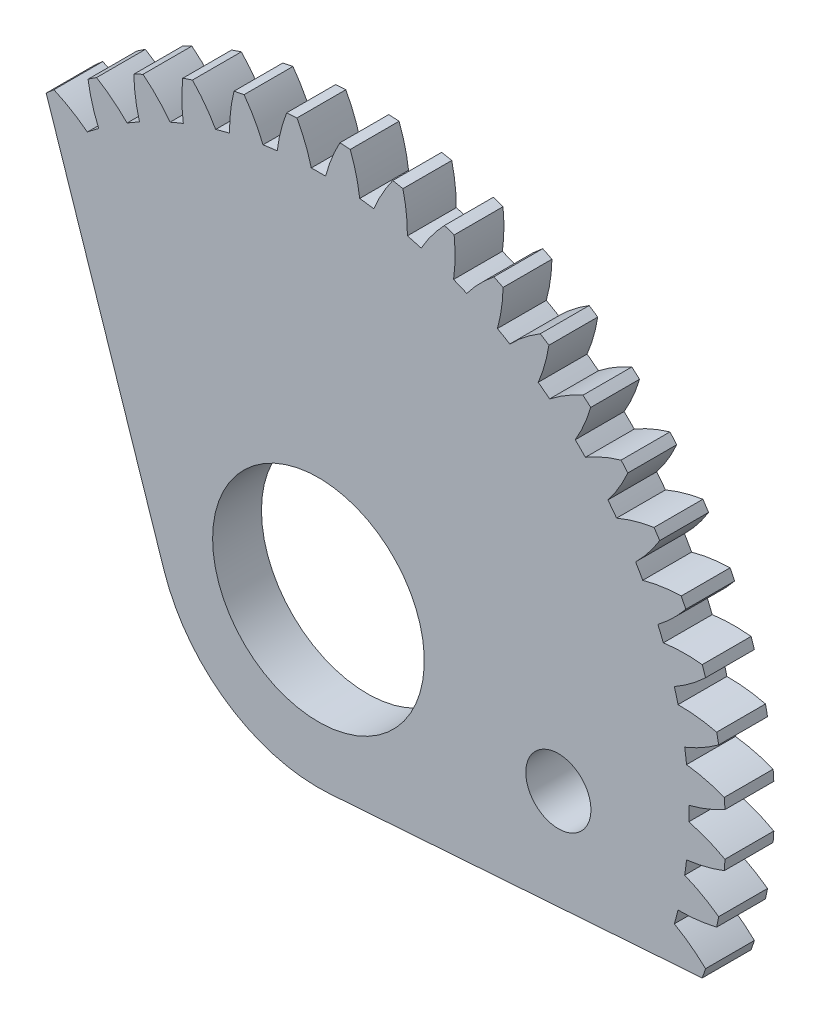
SolidWorks part; units mm, degrees
ref_plane "前视基准面" through (0, 0, 0) normal (0, 0, 1) x (1, 0, 0)
ref_plane "上视基准面" through (0, 0, 0) normal (0, 1, 0) x (1, 0, 0)
ref_plane "右视基准面" through (0, 0, 0) normal (1, 0, 0) x (0, 0, -1)
sketch "草图1" plane through (0, 0, 0) normal (0, 0, 1) x (1, 0, 0)
  arc A384 (-24.9651, 1.32) -> (-22.7448, 0.4395) centre (-20.3436, 9.7344) ccw
  arc A385 (-22.7448, 0.4395) -> (-22.7448, -0.4395) centre (0, 0) ccw
  arc A386 (-22.7448, -0.4395) -> (-24.9651, -1.32) centre (-20.3436, -9.7344) ccw
  arc A387 (-24.9651, -1.32) -> (-24.9238, -1.9499) centre (0, 0) ccw
  arc A388 (-24.9238, -1.9499) -> (-22.6075, -2.533) centre (-21.4402, 6.9957) ccw
  arc A389 (-22.6075, -2.533) -> (-22.4928, -3.4045) centre (0, 0) ccw
  arc A390 (-22.4928, -3.4045) -> (-24.5793, -4.5673) centre (-18.899, -12.3065) ccw
  arc A391 (-24.5793, -4.5673) -> (-24.4561, -5.1864) centre (0, 0) ccw
  arc A392 (-24.4561, -5.1864) -> (-22.0835, -5.4622) centre (-22.1699, 4.1374) ccw
  arc A393 (-22.0835, -5.4622) -> (-21.856, -6.3113) centre (0, 0) ccw
  arc A394 (-21.856, -6.3113) -> (-23.7728, -7.7365) centre (-17.131, -14.668) ccw
  arc A395 (-23.7728, -7.7365) -> (-23.5699, -8.3342) centre (0, 0) ccw
  arc A396 (-23.5699, -8.3342) -> (-21.1816, -8.298) centre (-22.5202, 1.2082) ccw
  arc A397 (-21.1816, -8.298) -> (-20.8452, -9.1101) centre (0, 0) ccw
  arc A398 (-20.8452, -9.1101) -> (-22.5596, -10.7733) centre (-15.0699, -16.7786) ccw
  arc A399 (-22.5596, -10.7733) -> (-22.2804, -11.3394) centre (0, 0) ccw
  arc A400 (-22.2804, -11.3394) -> (-19.9173, -10.9917) centre (-22.4853, -1.7416) ccw
  arc A401 (-19.9173, -10.9917) -> (-19.4778, -11.753) centre (0, 0) ccw
  arc A402 (-19.4778, -11.753) -> (-20.9604, -13.6257) centre (-12.7509, -18.602) ccw
  arc A403 (-20.9604, -13.6257) -> (-20.6097, -14.1506) centre (0, 0) ccw
  arc A404 (-20.6097, -14.1506) -> (-18.3122, -13.4974) centre (-22.0656, -4.6616) ccw
  arc A405 (-18.3122, -13.4974) -> (-17.7771, -14.1948) centre (0, 0) ccw
  arc A406 (-17.7771, -14.1948) -> (-19.0026, -16.245) centre (-10.2138, -20.1072) ccw
  arc A407 (-19.0026, -16.245) -> (-18.5864, -16.7196) centre (0, 0) ccw
  arc A408 (-18.5864, -16.7196) -> (-16.3938, -15.7722) centre (-21.2684, -7.5019) ccw
  arc A409 (-16.3938, -15.7722) -> (-15.7722, -16.3938) centre (0, 0) ccw
  arc A410 (-15.7722, -16.3938) -> (-16.7196, -18.5864) centre (-7.5019, -21.2684) ccw
  arc A411 (-16.7196, -18.5864) -> (-16.245, -19.0026) centre (0, 0) ccw
  arc A412 (-16.245, -19.0026) -> (-14.1948, -17.7771) centre (-20.1072, -10.2138) ccw
  arc A413 (-14.1948, -17.7771) -> (-13.4974, -18.3122) centre (0, 0) ccw
  arc A414 (-13.4974, -18.3122) -> (-14.1506, -20.6097) centre (-4.6616, -22.0656) ccw
  arc A415 (-14.1506, -20.6097) -> (-13.6257, -20.9604) centre (0, 0) ccw
  arc A416 (-13.6257, -20.9604) -> (-11.753, -19.4778) centre (-18.602, -12.7509) ccw
  arc A417 (-11.753, -19.4778) -> (-10.9917, -19.9173) centre (0, 0) ccw
  arc A418 (-10.9917, -19.9173) -> (-11.3394, -22.2804) centre (-1.7416, -22.4853) ccw
  arc A419 (-11.3394, -22.2804) -> (-10.7733, -22.5596) centre (0, 0) ccw
  arc A420 (-10.7733, -22.5596) -> (-9.1101, -20.8452) centre (-16.7786, -15.0699) ccw
  arc A421 (-9.1101, -20.8452) -> (-8.298, -21.1816) centre (0, 0) ccw
  arc A422 (-8.298, -21.1816) -> (-8.3342, -23.5699) centre (1.2082, -22.5202) ccw
  arc A423 (-8.3342, -23.5699) -> (-7.7365, -23.7728) centre (0, 0) ccw
  arc A424 (-7.7365, -23.7728) -> (-6.3113, -21.856) centre (-14.668, -17.131) ccw
  arc A425 (-6.3113, -21.856) -> (-5.4622, -22.0835) centre (0, 0) ccw
  arc A426 (-5.4622, -22.0835) -> (-5.1864, -24.4561) centre (4.1374, -22.1699) ccw
  arc A427 (-5.1864, -24.4561) -> (-4.5673, -24.5793) centre (0, 0) ccw
  arc A428 (-4.5673, -24.5793) -> (-3.4045, -22.4928) centre (-12.3065, -18.899) ccw
  arc A429 (-3.4045, -22.4928) -> (-2.533, -22.6075) centre (0, 0) ccw
  arc A430 (-2.533, -22.6075) -> (-1.9499, -24.9238) centre (6.9957, -21.4402) ccw
  arc A431 (-1.9499, -24.9238) -> (-1.32, -24.9651) centre (0, 0) ccw
  arc A432 (-1.32, -24.9651) -> (-0.4395, -22.7448) centre (-9.7344, -20.3436) ccw
  arc A433 (-0.4395, -22.7448) -> (0.4395, -22.7448) centre (0, 0) ccw
  arc A434 (0.4395, -22.7448) -> (1.32, -24.9651) centre (9.7344, -20.3436) ccw
  arc A435 (1.32, -24.9651) -> (1.9499, -24.9238) centre (0, 0) ccw
  arc A436 (1.9499, -24.9238) -> (2.533, -22.6075) centre (-6.9957, -21.4402) ccw
  arc A437 (2.533, -22.6075) -> (3.4045, -22.4928) centre (0, 0) ccw
  arc A438 (3.4045, -22.4928) -> (4.5673, -24.5793) centre (12.3065, -18.899) ccw
  arc A439 (4.5673, -24.5793) -> (5.1864, -24.4561) centre (0, 0) ccw
  arc A440 (5.1864, -24.4561) -> (5.4622, -22.0835) centre (-4.1374, -22.1699) ccw
  arc A441 (5.4622, -22.0835) -> (6.3113, -21.856) centre (0, 0) ccw
  arc A442 (6.3113, -21.856) -> (7.7365, -23.7728) centre (14.668, -17.131) ccw
  arc A443 (7.7365, -23.7728) -> (8.3342, -23.5699) centre (0, 0) ccw
  arc A444 (8.3342, -23.5699) -> (8.298, -21.1816) centre (-1.2082, -22.5202) ccw
  arc A445 (8.298, -21.1816) -> (9.1101, -20.8452) centre (0, 0) ccw
  arc A446 (9.1101, -20.8452) -> (10.7733, -22.5596) centre (16.7786, -15.0699) ccw
  arc A447 (10.7733, -22.5596) -> (11.3394, -22.2804) centre (0, 0) ccw
  arc A448 (11.3394, -22.2804) -> (10.9917, -19.9173) centre (1.7416, -22.4853) ccw
  arc A449 (10.9917, -19.9173) -> (11.753, -19.4778) centre (0, 0) ccw
  arc A450 (11.753, -19.4778) -> (13.6257, -20.9604) centre (18.602, -12.7509) ccw
  arc A451 (13.6257, -20.9604) -> (14.1506, -20.6097) centre (0, 0) ccw
  arc A452 (14.1506, -20.6097) -> (13.4974, -18.3122) centre (4.6616, -22.0656) ccw
  arc A453 (13.4974, -18.3122) -> (14.1948, -17.7771) centre (0, 0) ccw
  arc A454 (14.1948, -17.7771) -> (16.245, -19.0026) centre (20.1072, -10.2138) ccw
  arc A455 (16.245, -19.0026) -> (16.7196, -18.5864) centre (0, 0) ccw
  arc A456 (16.7196, -18.5864) -> (15.7722, -16.3938) centre (7.5019, -21.2684) ccw
  arc A457 (15.7722, -16.3938) -> (16.3938, -15.7722) centre (0, 0) ccw
  arc A458 (16.3938, -15.7722) -> (18.5864, -16.7196) centre (21.2684, -7.5019) ccw
  arc A459 (18.5864, -16.7196) -> (19.0026, -16.245) centre (0, 0) ccw
  arc A460 (19.0026, -16.245) -> (17.7771, -14.1948) centre (10.2138, -20.1072) ccw
  arc A461 (17.7771, -14.1948) -> (18.3122, -13.4974) centre (0, 0) ccw
  arc A462 (18.3122, -13.4974) -> (20.6097, -14.1506) centre (22.0656, -4.6616) ccw
  arc A463 (20.6097, -14.1506) -> (20.9604, -13.6257) centre (0, 0) ccw
  arc A464 (20.9604, -13.6257) -> (19.4778, -11.753) centre (12.7509, -18.602) ccw
  arc A465 (19.4778, -11.753) -> (19.9173, -10.9917) centre (0, 0) ccw
  arc A466 (19.9173, -10.9917) -> (22.2804, -11.3394) centre (22.4853, -1.7416) ccw
  arc A467 (22.2804, -11.3394) -> (22.5596, -10.7733) centre (0, 0) ccw
  arc A468 (22.5596, -10.7733) -> (20.8452, -9.1101) centre (15.0699, -16.7786) ccw
  arc A469 (20.8452, -9.1101) -> (21.1816, -8.298) centre (0, 0) ccw
  arc A470 (21.1816, -8.298) -> (23.5699, -8.3342) centre (22.5202, 1.2082) ccw
  arc A471 (23.5699, -8.3342) -> (23.7728, -7.7365) centre (0, 0) ccw
  arc A472 (23.7728, -7.7365) -> (21.856, -6.3113) centre (17.131, -14.668) ccw
  arc A473 (21.856, -6.3113) -> (22.0835, -5.4622) centre (0, 0) ccw
  arc A474 (22.0835, -5.4622) -> (24.4561, -5.1864) centre (22.1699, 4.1374) ccw
  arc A475 (24.4561, -5.1864) -> (24.5793, -4.5673) centre (0, 0) ccw
  arc A476 (24.5793, -4.5673) -> (22.4928, -3.4045) centre (18.899, -12.3065) ccw
  arc A477 (22.4928, -3.4045) -> (22.6075, -2.533) centre (0, 0) ccw
  arc A478 (22.6075, -2.533) -> (24.9238, -1.9499) centre (21.4402, 6.9957) ccw
  arc A479 (24.9238, -1.9499) -> (24.9651, -1.32) centre (0, 0) ccw
  arc A480 (24.9651, -1.32) -> (22.7448, -0.4395) centre (20.3436, -9.7344) ccw
  arc A481 (22.7448, -0.4395) -> (22.7448, 0.4395) centre (0, 0) ccw
  arc A482 (22.7448, 0.4395) -> (24.9651, 1.32) centre (20.3436, 9.7344) ccw
  arc A483 (24.9651, 1.32) -> (24.9238, 1.9499) centre (0, 0) ccw
  arc A484 (24.9238, 1.9499) -> (22.6075, 2.533) centre (21.4402, -6.9957) ccw
  arc A485 (22.6075, 2.533) -> (22.4928, 3.4045) centre (0, 0) ccw
  arc A486 (22.4928, 3.4045) -> (24.5793, 4.5673) centre (18.899, 12.3065) ccw
  arc A487 (24.5793, 4.5673) -> (24.4561, 5.1864) centre (0, 0) ccw
  arc A488 (24.4561, 5.1864) -> (22.0835, 5.4622) centre (22.1699, -4.1374) ccw
  arc A489 (22.0835, 5.4622) -> (21.856, 6.3113) centre (0, 0) ccw
  arc A490 (21.856, 6.3113) -> (23.7728, 7.7365) centre (17.131, 14.668) ccw
  arc A491 (23.7728, 7.7365) -> (23.5699, 8.3342) centre (0, 0) ccw
  arc A492 (23.5699, 8.3342) -> (21.1816, 8.298) centre (22.5202, -1.2082) ccw
  arc A493 (21.1816, 8.298) -> (20.8452, 9.1101) centre (0, 0) ccw
  arc A494 (20.8452, 9.1101) -> (22.5596, 10.7733) centre (15.0699, 16.7786) ccw
  arc A495 (22.5596, 10.7733) -> (22.2804, 11.3394) centre (0, 0) ccw
  arc A496 (22.2804, 11.3394) -> (19.9173, 10.9917) centre (22.4853, 1.7416) ccw
  arc A497 (19.9173, 10.9917) -> (19.4778, 11.753) centre (0, 0) ccw
  arc A498 (19.4778, 11.753) -> (20.9604, 13.6257) centre (12.7509, 18.602) ccw
  arc A499 (20.9604, 13.6257) -> (20.6097, 14.1506) centre (0, 0) ccw
  arc A500 (20.6097, 14.1506) -> (18.3122, 13.4974) centre (22.0656, 4.6616) ccw
  arc A501 (18.3122, 13.4974) -> (17.7771, 14.1948) centre (0, 0) ccw
  arc A502 (17.7771, 14.1948) -> (19.0026, 16.245) centre (10.2138, 20.1072) ccw
  arc A503 (19.0026, 16.245) -> (18.5864, 16.7196) centre (0, 0) ccw
  arc A504 (18.5864, 16.7196) -> (16.3938, 15.7722) centre (21.2684, 7.5019) ccw
  arc A505 (16.3938, 15.7722) -> (15.7722, 16.3938) centre (0, 0) ccw
  arc A506 (15.7722, 16.3938) -> (16.7196, 18.5864) centre (7.5019, 21.2684) ccw
  arc A507 (16.7196, 18.5864) -> (16.245, 19.0026) centre (0, 0) ccw
  arc A508 (16.245, 19.0026) -> (14.1948, 17.7771) centre (20.1072, 10.2138) ccw
  arc A509 (14.1948, 17.7771) -> (13.4974, 18.3122) centre (0, 0) ccw
  arc A510 (13.4974, 18.3122) -> (14.1506, 20.6097) centre (4.6616, 22.0656) ccw
  arc A511 (14.1506, 20.6097) -> (13.6257, 20.9604) centre (0, 0) ccw
  arc A512 (13.6257, 20.9604) -> (11.753, 19.4778) centre (18.602, 12.7509) ccw
  arc A513 (11.753, 19.4778) -> (10.9917, 19.9173) centre (0, 0) ccw
  arc A514 (10.9917, 19.9173) -> (11.3394, 22.2804) centre (1.7416, 22.4853) ccw
  arc A515 (11.3394, 22.2804) -> (10.7733, 22.5596) centre (0, 0) ccw
  arc A516 (10.7733, 22.5596) -> (9.1101, 20.8452) centre (16.7786, 15.0699) ccw
  arc A517 (9.1101, 20.8452) -> (8.298, 21.1816) centre (0, 0) ccw
  arc A518 (8.298, 21.1816) -> (8.3342, 23.5699) centre (-1.2082, 22.5202) ccw
  arc A519 (8.3342, 23.5699) -> (7.7365, 23.7728) centre (0, 0) ccw
  arc A520 (7.7365, 23.7728) -> (6.3113, 21.856) centre (14.668, 17.131) ccw
  arc A521 (6.3113, 21.856) -> (5.4622, 22.0835) centre (0, 0) ccw
  arc A522 (5.4622, 22.0835) -> (5.1864, 24.4561) centre (-4.1374, 22.1699) ccw
  arc A523 (5.1864, 24.4561) -> (4.5673, 24.5793) centre (0, 0) ccw
  arc A524 (4.5673, 24.5793) -> (3.4045, 22.4928) centre (12.3065, 18.899) ccw
  arc A525 (3.4045, 22.4928) -> (2.533, 22.6075) centre (0, 0) ccw
  arc A526 (2.533, 22.6075) -> (1.9499, 24.9238) centre (-6.9957, 21.4402) ccw
  arc A527 (1.9499, 24.9238) -> (1.32, 24.9651) centre (0, 0) ccw
  arc A528 (1.32, 24.9651) -> (0.4395, 22.7448) centre (9.7344, 20.3436) ccw
  arc A529 (0.4395, 22.7448) -> (-0.4395, 22.7448) centre (0, 0) ccw
  arc A530 (-0.4395, 22.7448) -> (-1.32, 24.9651) centre (-9.7344, 20.3436) ccw
  arc A531 (-1.32, 24.9651) -> (-1.9499, 24.9238) centre (0, 0) ccw
  arc A532 (-1.9499, 24.9238) -> (-2.533, 22.6075) centre (6.9957, 21.4402) ccw
  arc A533 (-2.533, 22.6075) -> (-3.4045, 22.4928) centre (0, 0) ccw
  arc A534 (-3.4045, 22.4928) -> (-4.5673, 24.5793) centre (-12.3065, 18.899) ccw
  arc A535 (-4.5673, 24.5793) -> (-5.1864, 24.4561) centre (0, 0) ccw
  arc A536 (-5.1864, 24.4561) -> (-5.4622, 22.0835) centre (4.1374, 22.1699) ccw
  arc A537 (-5.4622, 22.0835) -> (-6.3113, 21.856) centre (0, 0) ccw
  arc A538 (-6.3113, 21.856) -> (-7.7365, 23.7728) centre (-14.668, 17.131) ccw
  arc A539 (-7.7365, 23.7728) -> (-8.3342, 23.5699) centre (0, 0) ccw
  arc A540 (-8.3342, 23.5699) -> (-8.298, 21.1816) centre (1.2082, 22.5202) ccw
  arc A541 (-8.298, 21.1816) -> (-9.1101, 20.8452) centre (0, 0) ccw
  arc A542 (-9.1101, 20.8452) -> (-10.7733, 22.5596) centre (-16.7786, 15.0699) ccw
  arc A543 (-10.7733, 22.5596) -> (-11.3394, 22.2804) centre (0, 0) ccw
  arc A544 (-11.3394, 22.2804) -> (-10.9917, 19.9173) centre (-1.7416, 22.4853) ccw
  arc A545 (-10.9917, 19.9173) -> (-11.753, 19.4778) centre (0, 0) ccw
  arc A546 (-11.753, 19.4778) -> (-13.6257, 20.9604) centre (-18.602, 12.7509) ccw
  arc A547 (-13.6257, 20.9604) -> (-14.1506, 20.6097) centre (0, 0) ccw
  arc A548 (-14.1506, 20.6097) -> (-13.4974, 18.3122) centre (-4.6616, 22.0656) ccw
  arc A549 (-13.4974, 18.3122) -> (-14.1948, 17.7771) centre (0, 0) ccw
  arc A550 (-14.1948, 17.7771) -> (-16.245, 19.0026) centre (-20.1072, 10.2138) ccw
  arc A551 (-16.245, 19.0026) -> (-16.7196, 18.5864) centre (0, 0) ccw
  arc A552 (-16.7196, 18.5864) -> (-15.7722, 16.3938) centre (-7.5019, 21.2684) ccw
  arc A553 (-15.7722, 16.3938) -> (-16.3938, 15.7722) centre (0, 0) ccw
  arc A554 (-16.3938, 15.7722) -> (-18.5864, 16.7196) centre (-21.2684, 7.5019) ccw
  arc A555 (-18.5864, 16.7196) -> (-19.0026, 16.245) centre (0, 0) ccw
  arc A556 (-19.0026, 16.245) -> (-17.7771, 14.1948) centre (-10.2138, 20.1072) ccw
  arc A557 (-17.7771, 14.1948) -> (-18.3122, 13.4974) centre (0, 0) ccw
  arc A558 (-18.3122, 13.4974) -> (-20.6097, 14.1506) centre (-22.0656, 4.6616) ccw
  arc A559 (-20.6097, 14.1506) -> (-20.9604, 13.6257) centre (0, 0) ccw
  arc A560 (-20.9604, 13.6257) -> (-19.4778, 11.753) centre (-12.7509, 18.602) ccw
  arc A561 (-19.4778, 11.753) -> (-19.9173, 10.9917) centre (0, 0) ccw
  arc A562 (-19.9173, 10.9917) -> (-22.2804, 11.3394) centre (-22.4853, 1.7416) ccw
  arc A563 (-22.2804, 11.3394) -> (-22.5596, 10.7733) centre (0, 0) ccw
  arc A564 (-22.5596, 10.7733) -> (-20.8452, 9.1101) centre (-15.0699, 16.7786) ccw
  arc A565 (-20.8452, 9.1101) -> (-21.1816, 8.298) centre (0, 0) ccw
  arc A566 (-21.1816, 8.298) -> (-23.5699, 8.3342) centre (-22.5202, -1.2082) ccw
  arc A567 (-23.5699, 8.3342) -> (-23.7728, 7.7365) centre (0, 0) ccw
  arc A568 (-23.7728, 7.7365) -> (-21.856, 6.3113) centre (-17.131, 14.668) ccw
  arc A569 (-21.856, 6.3113) -> (-22.0835, 5.4622) centre (0, 0) ccw
  arc A570 (-22.0835, 5.4622) -> (-24.4561, 5.1864) centre (-22.1699, -4.1374) ccw
  arc A571 (-24.4561, 5.1864) -> (-24.5793, 4.5673) centre (0, 0) ccw
  arc A572 (-24.5793, 4.5673) -> (-22.4928, 3.4045) centre (-18.899, 12.3065) ccw
  arc A573 (-22.4928, 3.4045) -> (-22.6075, 2.533) centre (0, 0) ccw
  arc A574 (-22.6075, 2.533) -> (-24.9238, 1.9499) centre (-21.4402, -6.9957) ccw
  arc A575 (-24.9238, 1.9499) -> (-24.9651, 1.32) centre (0, 0) ccw
extrude "凸台-拉伸1" add sketch "草图1" along normal blind 5
sketch "草图2" plane through (0, 0, 0) normal (0, 0, -1) x (-1, 0, 0)
  line L0 (-21.1816, -8.298) -> (0.4239, -6.9872)
  line L1 (15.7722, 16.3938) -> (6.2931, -3.0655)
  line L2 (-21.1816, -8.298) -> (-28.2807, -11.3394)
  line L3 (-28.2807, -11.3394) -> (-10.7733, -28.619)
  line L4 (-10.7733, -28.619) -> (32.4685, -23.5699)
  line L5 (32.4685, -23.5699) -> (27.6641, 23.5699)
  line L6 (27.6641, 23.5699) -> (15.7722, 16.3938)
  circle A0 centre (0, 0) radius 7
  arc A193 (24.9651, 1.32) -> (24.9238, 1.9499) centre (0, 0) ccw
  arc A194 (24.9238, 1.9499) -> (22.6075, 2.533) centre (21.4402, -6.9957) ccw
  arc A195 (22.6075, 2.533) -> (22.4928, 3.4045) centre (0, 0) ccw
  arc A196 (22.4928, 3.4045) -> (24.5793, 4.5673) centre (18.899, 12.3065) ccw
  arc A197 (24.5793, 4.5673) -> (24.4561, 5.1864) centre (0, 0) ccw
  arc A198 (24.4561, 5.1864) -> (22.0835, 5.4622) centre (22.1699, -4.1374) ccw
  arc A199 (22.0835, 5.4622) -> (21.856, 6.3113) centre (0, 0) ccw
  arc A200 (21.856, 6.3113) -> (23.7728, 7.7365) centre (17.131, 14.668) ccw
  arc A201 (23.7728, 7.7365) -> (23.5699, 8.3342) centre (0, 0) ccw
  arc A202 (23.5699, 8.3342) -> (21.1816, 8.298) centre (22.5202, -1.2082) ccw
  arc A203 (21.1816, 8.298) -> (20.8452, 9.1101) centre (0, 0) ccw
  arc A204 (20.8452, 9.1101) -> (22.5596, 10.7733) centre (15.0699, 16.7786) ccw
  arc A205 (22.5596, 10.7733) -> (22.2804, 11.3394) centre (0, 0) ccw
  arc A206 (22.2804, 11.3394) -> (19.9173, 10.9917) centre (22.4853, 1.7416) ccw
  arc A207 (19.9173, 10.9917) -> (19.4778, 11.753) centre (0, 0) ccw
  arc A208 (19.4778, 11.753) -> (20.9604, 13.6257) centre (12.7509, 18.602) ccw
  arc A209 (20.9604, 13.6257) -> (20.6097, 14.1506) centre (0, 0) ccw
  arc A210 (20.6097, 14.1506) -> (18.3122, 13.4974) centre (22.0656, 4.6616) ccw
  arc A211 (18.3122, 13.4974) -> (17.7771, 14.1948) centre (0, 0) ccw
  arc A212 (17.7771, 14.1948) -> (19.0026, 16.245) centre (10.2138, 20.1072) ccw
  arc A213 (19.0026, 16.245) -> (18.5864, 16.7196) centre (0, 0) ccw
  arc A214 (18.5864, 16.7196) -> (16.3938, 15.7722) centre (21.2684, 7.5019) ccw
  arc A215 (16.3938, 15.7722) -> (15.7722, 16.3938) centre (0, 0) ccw
  arc A216 (15.7722, 16.3938) -> (16.7196, 18.5864) centre (7.5019, 21.2684) ccw
  arc A217 (16.7196, 18.5864) -> (16.245, 19.0026) centre (0, 0) ccw
  arc A218 (16.245, 19.0026) -> (14.1948, 17.7771) centre (20.1072, 10.2138) ccw
  arc A219 (14.1948, 17.7771) -> (13.4974, 18.3122) centre (0, 0) ccw
  arc A220 (13.4974, 18.3122) -> (14.1506, 20.6097) centre (4.6616, 22.0656) ccw
  arc A221 (14.1506, 20.6097) -> (13.6257, 20.9604) centre (0, 0) ccw
  arc A222 (13.6257, 20.9604) -> (11.753, 19.4778) centre (18.602, 12.7509) ccw
  arc A223 (11.753, 19.4778) -> (10.9917, 19.9173) centre (0, 0) ccw
  arc A224 (10.9917, 19.9173) -> (11.3394, 22.2804) centre (1.7416, 22.4853) ccw
  arc A225 (11.3394, 22.2804) -> (10.7733, 22.5596) centre (0, 0) ccw
  arc A226 (10.7733, 22.5596) -> (9.1101, 20.8452) centre (16.7786, 15.0699) ccw
  arc A227 (9.1101, 20.8452) -> (8.298, 21.1816) centre (0, 0) ccw
  arc A228 (8.298, 21.1816) -> (8.3342, 23.5699) centre (-1.2082, 22.5202) ccw
  arc A229 (8.3342, 23.5699) -> (7.7365, 23.7728) centre (0, 0) ccw
  arc A230 (7.7365, 23.7728) -> (6.3113, 21.856) centre (14.668, 17.131) ccw
  arc A231 (6.3113, 21.856) -> (5.4622, 22.0835) centre (0, 0) ccw
  arc A232 (5.4622, 22.0835) -> (5.1864, 24.4561) centre (-4.1374, 22.1699) ccw
  arc A233 (5.1864, 24.4561) -> (4.5673, 24.5793) centre (0, 0) ccw
  arc A234 (4.5673, 24.5793) -> (3.4045, 22.4928) centre (12.3065, 18.899) ccw
  arc A235 (3.4045, 22.4928) -> (2.533, 22.6075) centre (0, 0) ccw
  arc A236 (2.533, 22.6075) -> (1.9499, 24.9238) centre (-6.9957, 21.4402) ccw
  arc A237 (1.9499, 24.9238) -> (1.32, 24.9651) centre (0, 0) ccw
  arc A238 (1.32, 24.9651) -> (0.4395, 22.7448) centre (9.7344, 20.3436) ccw
  arc A239 (0.4395, 22.7448) -> (-0.4395, 22.7448) centre (0, 0) ccw
  arc A240 (-0.4395, 22.7448) -> (-1.32, 24.9651) centre (-9.7344, 20.3436) ccw
  arc A241 (-1.32, 24.9651) -> (-1.9499, 24.9238) centre (0, 0) ccw
  arc A242 (-1.9499, 24.9238) -> (-2.533, 22.6075) centre (6.9957, 21.4402) ccw
  arc A243 (-2.533, 22.6075) -> (-3.4045, 22.4928) centre (0, 0) ccw
  arc A244 (-3.4045, 22.4928) -> (-4.5673, 24.5793) centre (-12.3065, 18.899) ccw
  arc A245 (-4.5673, 24.5793) -> (-5.1864, 24.4561) centre (0, 0) ccw
  arc A246 (-5.1864, 24.4561) -> (-5.4622, 22.0835) centre (4.1374, 22.1699) ccw
  arc A247 (-5.4622, 22.0835) -> (-6.3113, 21.856) centre (0, 0) ccw
  arc A248 (-6.3113, 21.856) -> (-7.7365, 23.7728) centre (-14.668, 17.131) ccw
  arc A249 (-7.7365, 23.7728) -> (-8.3342, 23.5699) centre (0, 0) ccw
  arc A250 (-8.3342, 23.5699) -> (-8.298, 21.1816) centre (1.2082, 22.5202) ccw
  arc A251 (-8.298, 21.1816) -> (-9.1101, 20.8452) centre (0, 0) ccw
  arc A252 (-9.1101, 20.8452) -> (-10.7733, 22.5596) centre (-16.7786, 15.0699) ccw
  arc A253 (-10.7733, 22.5596) -> (-11.3394, 22.2804) centre (0, 0) ccw
  arc A254 (-11.3394, 22.2804) -> (-10.9917, 19.9173) centre (-1.7416, 22.4853) ccw
  arc A255 (-10.9917, 19.9173) -> (-11.753, 19.4778) centre (0, 0) ccw
  arc A256 (-11.753, 19.4778) -> (-13.6257, 20.9604) centre (-18.602, 12.7509) ccw
  arc A257 (-13.6257, 20.9604) -> (-14.1506, 20.6097) centre (0, 0) ccw
  arc A258 (-14.1506, 20.6097) -> (-13.4974, 18.3122) centre (-4.6616, 22.0656) ccw
  arc A259 (-13.4974, 18.3122) -> (-14.1948, 17.7771) centre (0, 0) ccw
  arc A260 (-14.1948, 17.7771) -> (-16.245, 19.0026) centre (-20.1072, 10.2138) ccw
  arc A261 (-16.245, 19.0026) -> (-16.7196, 18.5864) centre (0, 0) ccw
  arc A262 (-16.7196, 18.5864) -> (-15.7722, 16.3938) centre (-7.5019, 21.2684) ccw
  arc A263 (-15.7722, 16.3938) -> (-16.3938, 15.7722) centre (0, 0) ccw
  arc A264 (-16.3938, 15.7722) -> (-18.5864, 16.7196) centre (-21.2684, 7.5019) ccw
  arc A265 (-18.5864, 16.7196) -> (-19.0026, 16.245) centre (0, 0) ccw
  arc A266 (-19.0026, 16.245) -> (-17.7771, 14.1948) centre (-10.2138, 20.1072) ccw
  arc A267 (-17.7771, 14.1948) -> (-18.3122, 13.4974) centre (0, 0) ccw
  arc A268 (-18.3122, 13.4974) -> (-20.6097, 14.1506) centre (-22.0656, 4.6616) ccw
  arc A269 (-20.6097, 14.1506) -> (-20.9604, 13.6257) centre (0, 0) ccw
  arc A270 (-20.9604, 13.6257) -> (-19.4778, 11.753) centre (-12.7509, 18.602) ccw
  arc A271 (-19.4778, 11.753) -> (-19.9173, 10.9917) centre (0, 0) ccw
  arc A272 (-19.9173, 10.9917) -> (-22.2804, 11.3394) centre (-22.4853, 1.7416) ccw
  arc A273 (-22.2804, 11.3394) -> (-22.5596, 10.7733) centre (0, 0) ccw
  arc A274 (-22.5596, 10.7733) -> (-20.8452, 9.1101) centre (-15.0699, 16.7786) ccw
  arc A275 (-20.8452, 9.1101) -> (-21.1816, 8.298) centre (0, 0) ccw
  arc A276 (-21.1816, 8.298) -> (-23.5699, 8.3342) centre (-22.5202, -1.2082) ccw
  arc A277 (-23.5699, 8.3342) -> (-23.7728, 7.7365) centre (0, 0) ccw
  arc A278 (-23.7728, 7.7365) -> (-21.856, 6.3113) centre (-17.131, 14.668) ccw
  arc A279 (-21.856, 6.3113) -> (-22.0835, 5.4622) centre (0, 0) ccw
  arc A280 (-22.0835, 5.4622) -> (-24.4561, 5.1864) centre (-22.1699, -4.1374) ccw
  arc A281 (-24.4561, 5.1864) -> (-24.5793, 4.5673) centre (0, 0) ccw
  arc A282 (-24.5793, 4.5673) -> (-22.4928, 3.4045) centre (-18.899, 12.3065) ccw
  arc A283 (-22.4928, 3.4045) -> (-22.6075, 2.533) centre (0, 0) ccw
  arc A284 (-22.6075, 2.533) -> (-24.9238, 1.9499) centre (-21.4402, -6.9957) ccw
  arc A285 (-24.9238, 1.9499) -> (-24.9651, 1.32) centre (0, 0) ccw
  arc A286 (-24.9651, 1.32) -> (-22.7448, 0.4395) centre (-20.3436, 9.7344) ccw
  arc A287 (-22.7448, 0.4395) -> (-22.7448, -0.4395) centre (0, 0) ccw
  arc A288 (-22.7448, -0.4395) -> (-24.9651, -1.32) centre (-20.3436, -9.7344) ccw
  arc A289 (-24.9651, -1.32) -> (-24.9238, -1.9499) centre (0, 0) ccw
  arc A290 (-24.9238, -1.9499) -> (-22.6075, -2.533) centre (-21.4402, 6.9957) ccw
  arc A291 (-22.6075, -2.533) -> (-22.4928, -3.4045) centre (0, 0) ccw
  arc A292 (-22.4928, -3.4045) -> (-24.5793, -4.5673) centre (-18.899, -12.3065) ccw
  arc A293 (-24.5793, -4.5673) -> (-24.4561, -5.1864) centre (0, 0) ccw
  arc A294 (-24.4561, -5.1864) -> (-22.0835, -5.4622) centre (-22.1699, 4.1374) ccw
  arc A295 (-22.0835, -5.4622) -> (-21.856, -6.3113) centre (0, 0) ccw
  arc A296 (-21.856, -6.3113) -> (-23.7728, -7.7365) centre (-17.131, -14.668) ccw
  arc A297 (-23.7728, -7.7365) -> (-23.5699, -8.3342) centre (0, 0) ccw
  arc A298 (-23.5699, -8.3342) -> (-21.1816, -8.298) centre (-22.5202, 1.2082) ccw
  arc A299 (-21.1816, -8.298) -> (-20.8452, -9.1101) centre (0, 0) ccw
  arc A300 (-20.8452, -9.1101) -> (-22.5596, -10.7733) centre (-15.0699, -16.7786) ccw
  arc A301 (-22.5596, -10.7733) -> (-22.2804, -11.3394) centre (0, 0) ccw
  arc A302 (-22.2804, -11.3394) -> (-19.9173, -10.9917) centre (-22.4853, -1.7416) ccw
  arc A303 (-19.9173, -10.9917) -> (-19.4778, -11.753) centre (0, 0) ccw
  arc A304 (-19.4778, -11.753) -> (-20.9604, -13.6257) centre (-12.7509, -18.602) ccw
  arc A305 (-20.9604, -13.6257) -> (-20.6097, -14.1506) centre (0, 0) ccw
  arc A306 (-20.6097, -14.1506) -> (-18.3122, -13.4974) centre (-22.0656, -4.6616) ccw
  arc A307 (-18.3122, -13.4974) -> (-17.7771, -14.1948) centre (0, 0) ccw
  arc A308 (-17.7771, -14.1948) -> (-19.0026, -16.245) centre (-10.2138, -20.1072) ccw
  arc A309 (-19.0026, -16.245) -> (-18.5864, -16.7196) centre (0, 0) ccw
  arc A310 (-18.5864, -16.7196) -> (-16.3938, -15.7722) centre (-21.2684, -7.5019) ccw
  arc A311 (-16.3938, -15.7722) -> (-15.7722, -16.3938) centre (0, 0) ccw
  arc A312 (-15.7722, -16.3938) -> (-16.7196, -18.5864) centre (-7.5019, -21.2684) ccw
  arc A313 (-16.7196, -18.5864) -> (-16.245, -19.0026) centre (0, 0) ccw
  arc A314 (-16.245, -19.0026) -> (-14.1948, -17.7771) centre (-20.1072, -10.2138) ccw
  arc A315 (-14.1948, -17.7771) -> (-13.4974, -18.3122) centre (0, 0) ccw
  arc A316 (-13.4974, -18.3122) -> (-14.1506, -20.6097) centre (-4.6616, -22.0656) ccw
  arc A317 (-14.1506, -20.6097) -> (-13.6257, -20.9604) centre (0, 0) ccw
  arc A318 (-13.6257, -20.9604) -> (-11.753, -19.4778) centre (-18.602, -12.7509) ccw
  arc A319 (-11.753, -19.4778) -> (-10.9917, -19.9173) centre (0, 0) ccw
  arc A320 (-10.9917, -19.9173) -> (-11.3394, -22.2804) centre (-1.7416, -22.4853) ccw
  arc A321 (-11.3394, -22.2804) -> (-10.7733, -22.5596) centre (0, 0) ccw
  arc A322 (-10.7733, -22.5596) -> (-9.1101, -20.8452) centre (-16.7786, -15.0699) ccw
  arc A323 (-9.1101, -20.8452) -> (-8.298, -21.1816) centre (0, 0) ccw
  arc A324 (-8.298, -21.1816) -> (-8.3342, -23.5699) centre (1.2082, -22.5202) ccw
  arc A325 (-8.3342, -23.5699) -> (-7.7365, -23.7728) centre (0, 0) ccw
  arc A326 (-7.7365, -23.7728) -> (-6.3113, -21.856) centre (-14.668, -17.131) ccw
  arc A327 (-6.3113, -21.856) -> (-5.4622, -22.0835) centre (0, 0) ccw
  arc A328 (-5.4622, -22.0835) -> (-5.1864, -24.4561) centre (4.1374, -22.1699) ccw
  arc A329 (-5.1864, -24.4561) -> (-4.5673, -24.5793) centre (0, 0) ccw
  arc A330 (-4.5673, -24.5793) -> (-3.4045, -22.4928) centre (-12.3065, -18.899) ccw
  arc A331 (-3.4045, -22.4928) -> (-2.533, -22.6075) centre (0, 0) ccw
  arc A332 (-2.533, -22.6075) -> (-1.9499, -24.9238) centre (6.9957, -21.4402) ccw
  arc A333 (-1.9499, -24.9238) -> (-1.32, -24.9651) centre (0, 0) ccw
  arc A334 (-1.32, -24.9651) -> (-0.4395, -22.7448) centre (-9.7344, -20.3436) ccw
  arc A335 (-0.4395, -22.7448) -> (0.4395, -22.7448) centre (0, 0) ccw
  arc A336 (0.4395, -22.7448) -> (1.32, -24.9651) centre (9.7344, -20.3436) ccw
  arc A337 (1.32, -24.9651) -> (1.9499, -24.9238) centre (0, 0) ccw
  arc A338 (1.9499, -24.9238) -> (2.533, -22.6075) centre (-6.9957, -21.4402) ccw
  arc A339 (2.533, -22.6075) -> (3.4045, -22.4928) centre (0, 0) ccw
  arc A340 (3.4045, -22.4928) -> (4.5673, -24.5793) centre (12.3065, -18.899) ccw
  arc A341 (4.5673, -24.5793) -> (5.1864, -24.4561) centre (0, 0) ccw
  arc A342 (5.1864, -24.4561) -> (5.4622, -22.0835) centre (-4.1374, -22.1699) ccw
  arc A343 (5.4622, -22.0835) -> (6.3113, -21.856) centre (0, 0) ccw
  arc A344 (6.3113, -21.856) -> (7.7365, -23.7728) centre (14.668, -17.131) ccw
  arc A345 (7.7365, -23.7728) -> (8.3342, -23.5699) centre (0, 0) ccw
  arc A346 (8.3342, -23.5699) -> (8.298, -21.1816) centre (-1.2082, -22.5202) ccw
  arc A347 (8.298, -21.1816) -> (9.1101, -20.8452) centre (0, 0) ccw
  arc A348 (9.1101, -20.8452) -> (10.7733, -22.5596) centre (16.7786, -15.0699) ccw
  arc A349 (10.7733, -22.5596) -> (11.3394, -22.2804) centre (0, 0) ccw
  arc A350 (11.3394, -22.2804) -> (10.9917, -19.9173) centre (1.7416, -22.4853) ccw
  arc A351 (10.9917, -19.9173) -> (11.753, -19.4778) centre (0, 0) ccw
  arc A352 (11.753, -19.4778) -> (13.6257, -20.9604) centre (18.602, -12.7509) ccw
  arc A353 (13.6257, -20.9604) -> (14.1506, -20.6097) centre (0, 0) ccw
  arc A354 (14.1506, -20.6097) -> (13.4974, -18.3122) centre (4.6616, -22.0656) ccw
  arc A355 (13.4974, -18.3122) -> (14.1948, -17.7771) centre (0, 0) ccw
  arc A356 (14.1948, -17.7771) -> (16.245, -19.0026) centre (20.1072, -10.2138) ccw
  arc A357 (16.245, -19.0026) -> (16.7196, -18.5864) centre (0, 0) ccw
  arc A358 (16.7196, -18.5864) -> (15.7722, -16.3938) centre (7.5019, -21.2684) ccw
  arc A359 (15.7722, -16.3938) -> (16.3938, -15.7722) centre (0, 0) ccw
  arc A360 (16.3938, -15.7722) -> (18.5864, -16.7196) centre (21.2684, -7.5019) ccw
  arc A361 (18.5864, -16.7196) -> (19.0026, -16.245) centre (0, 0) ccw
  arc A362 (19.0026, -16.245) -> (17.7771, -14.1948) centre (10.2138, -20.1072) ccw
  arc A363 (17.7771, -14.1948) -> (18.3122, -13.4974) centre (0, 0) ccw
  arc A364 (18.3122, -13.4974) -> (20.6097, -14.1506) centre (22.0656, -4.6616) ccw
  arc A365 (20.6097, -14.1506) -> (20.9604, -13.6257) centre (0, 0) ccw
  arc A366 (20.9604, -13.6257) -> (19.4778, -11.753) centre (12.7509, -18.602) ccw
  arc A367 (19.4778, -11.753) -> (19.9173, -10.9917) centre (0, 0) ccw
  arc A368 (19.9173, -10.9917) -> (22.2804, -11.3394) centre (22.4853, -1.7416) ccw
  arc A369 (22.2804, -11.3394) -> (22.5596, -10.7733) centre (0, 0) ccw
  arc A370 (22.5596, -10.7733) -> (20.8452, -9.1101) centre (15.0699, -16.7786) ccw
  arc A371 (20.8452, -9.1101) -> (21.1816, -8.298) centre (0, 0) ccw
  arc A372 (21.1816, -8.298) -> (23.5699, -8.3342) centre (22.5202, 1.2082) ccw
  arc A373 (23.5699, -8.3342) -> (23.7728, -7.7365) centre (0, 0) ccw
  arc A374 (23.7728, -7.7365) -> (21.856, -6.3113) centre (17.131, -14.668) ccw
  arc A375 (21.856, -6.3113) -> (22.0835, -5.4622) centre (0, 0) ccw
  arc A376 (22.0835, -5.4622) -> (24.4561, -5.1864) centre (22.1699, 4.1374) ccw
  arc A377 (24.4561, -5.1864) -> (24.5793, -4.5673) centre (0, 0) ccw
  arc A378 (24.5793, -4.5673) -> (22.4928, -3.4045) centre (18.899, -12.3065) ccw
  arc A379 (22.4928, -3.4045) -> (22.6075, -2.533) centre (0, 0) ccw
  arc A380 (22.6075, -2.533) -> (24.9238, -1.9499) centre (21.4402, 6.9957) ccw
  arc A381 (24.9238, -1.9499) -> (24.9651, -1.32) centre (0, 0) ccw
  arc A382 (24.9651, -1.32) -> (22.7448, -0.4395) centre (20.3436, -9.7344) ccw
  arc A383 (22.7448, -0.4395) -> (22.7448, 0.4395) centre (0, 0) ccw
  arc A384 (22.7448, 0.4395) -> (24.9651, 1.32) centre (20.3436, 9.7344) ccw
  arc A385 (24.9651, 1.32) -> (24.9238, 1.9499) centre (0, 0) ccw
  arc A386 (24.9238, 1.9499) -> (22.6075, 2.533) centre (21.4402, -6.9957) ccw
  arc A387 (22.6075, 2.533) -> (22.4928, 3.4045) centre (0, 0) ccw
  arc A388 (22.4928, 3.4045) -> (24.5793, 4.5673) centre (18.899, 12.3065) ccw
  arc A389 (24.5793, 4.5673) -> (24.4561, 5.1864) centre (0, 0) ccw
  arc A390 (24.4561, 5.1864) -> (22.0835, 5.4622) centre (22.1699, -4.1374) ccw
  arc A391 (22.0835, 5.4622) -> (21.856, 6.3113) centre (0, 0) ccw
  arc A392 (21.856, 6.3113) -> (23.7728, 7.7365) centre (17.131, 14.668) ccw
  arc A393 (23.7728, 7.7365) -> (23.5699, 8.3342) centre (0, 0) ccw
  arc A394 (23.5699, 8.3342) -> (21.1816, 8.298) centre (22.5202, -1.2082) ccw
  arc A395 (21.1816, 8.298) -> (20.8452, 9.1101) centre (0, 0) ccw
  arc A396 (20.8452, 9.1101) -> (22.5596, 10.7733) centre (15.0699, 16.7786) ccw
  arc A397 (22.5596, 10.7733) -> (22.2804, 11.3394) centre (0, 0) ccw
  arc A398 (22.2804, 11.3394) -> (19.9173, 10.9917) centre (22.4853, 1.7416) ccw
  arc A399 (19.9173, 10.9917) -> (19.4778, 11.753) centre (0, 0) ccw
  arc A400 (19.4778, 11.753) -> (20.9604, 13.6257) centre (12.7509, 18.602) ccw
  arc A401 (20.9604, 13.6257) -> (20.6097, 14.1506) centre (0, 0) ccw
  arc A402 (20.6097, 14.1506) -> (18.3122, 13.4974) centre (22.0656, 4.6616) ccw
  arc A403 (18.3122, 13.4974) -> (17.7771, 14.1948) centre (0, 0) ccw
  arc A404 (17.7771, 14.1948) -> (19.0026, 16.245) centre (10.2138, 20.1072) ccw
  arc A405 (19.0026, 16.245) -> (18.5864, 16.7196) centre (0, 0) ccw
  arc A406 (18.5864, 16.7196) -> (16.3938, 15.7722) centre (21.2684, 7.5019) ccw
  arc A407 (16.3938, 15.7722) -> (15.7722, 16.3938) centre (0, 0) ccw
  arc A408 (15.7722, 16.3938) -> (16.7196, 18.5864) centre (7.5019, 21.2684) ccw
  arc A409 (16.7196, 18.5864) -> (16.245, 19.0026) centre (0, 0) ccw
  arc A410 (16.245, 19.0026) -> (14.1948, 17.7771) centre (20.1072, 10.2138) ccw
  arc A411 (14.1948, 17.7771) -> (13.4974, 18.3122) centre (0, 0) ccw
  arc A412 (13.4974, 18.3122) -> (14.1506, 20.6097) centre (4.6616, 22.0656) ccw
  arc A413 (14.1506, 20.6097) -> (13.6257, 20.9604) centre (0, 0) ccw
  arc A414 (13.6257, 20.9604) -> (11.753, 19.4778) centre (18.602, 12.7509) ccw
  arc A415 (11.753, 19.4778) -> (10.9917, 19.9173) centre (0, 0) ccw
  arc A416 (10.9917, 19.9173) -> (11.3394, 22.2804) centre (1.7416, 22.4853) ccw
  arc A417 (11.3394, 22.2804) -> (10.7733, 22.5596) centre (0, 0) ccw
  arc A418 (10.7733, 22.5596) -> (9.1101, 20.8452) centre (16.7786, 15.0699) ccw
  arc A419 (9.1101, 20.8452) -> (8.298, 21.1816) centre (0, 0) ccw
  arc A420 (8.298, 21.1816) -> (8.3342, 23.5699) centre (-1.2082, 22.5202) ccw
  arc A421 (8.3342, 23.5699) -> (7.7365, 23.7728) centre (0, 0) ccw
  arc A422 (7.7365, 23.7728) -> (6.3113, 21.856) centre (14.668, 17.131) ccw
  arc A423 (6.3113, 21.856) -> (5.4622, 22.0835) centre (0, 0) ccw
  arc A424 (5.4622, 22.0835) -> (5.1864, 24.4561) centre (-4.1374, 22.1699) ccw
  arc A425 (5.1864, 24.4561) -> (4.5673, 24.5793) centre (0, 0) ccw
  arc A426 (4.5673, 24.5793) -> (3.4045, 22.4928) centre (12.3065, 18.899) ccw
  arc A427 (3.4045, 22.4928) -> (2.533, 22.6075) centre (0, 0) ccw
  arc A428 (2.533, 22.6075) -> (1.9499, 24.9238) centre (-6.9957, 21.4402) ccw
  arc A429 (1.9499, 24.9238) -> (1.32, 24.9651) centre (0, 0) ccw
  arc A430 (1.32, 24.9651) -> (0.4395, 22.7448) centre (9.7344, 20.3436) ccw
  arc A431 (0.4395, 22.7448) -> (-0.4395, 22.7448) centre (0, 0) ccw
  arc A432 (-0.4395, 22.7448) -> (-1.32, 24.9651) centre (-9.7344, 20.3436) ccw
  arc A433 (-1.32, 24.9651) -> (-1.9499, 24.9238) centre (0, 0) ccw
  arc A434 (-1.9499, 24.9238) -> (-2.533, 22.6075) centre (6.9957, 21.4402) ccw
  arc A435 (-2.533, 22.6075) -> (-3.4045, 22.4928) centre (0, 0) ccw
  arc A436 (-3.4045, 22.4928) -> (-4.5673, 24.5793) centre (-12.3065, 18.899) ccw
  arc A437 (-4.5673, 24.5793) -> (-5.1864, 24.4561) centre (0, 0) ccw
  arc A438 (-5.1864, 24.4561) -> (-5.4622, 22.0835) centre (4.1374, 22.1699) ccw
  arc A439 (-5.4622, 22.0835) -> (-6.3113, 21.856) centre (0, 0) ccw
  arc A440 (-6.3113, 21.856) -> (-7.7365, 23.7728) centre (-14.668, 17.131) ccw
  arc A441 (-7.7365, 23.7728) -> (-8.3342, 23.5699) centre (0, 0) ccw
  arc A442 (-8.3342, 23.5699) -> (-8.298, 21.1816) centre (1.2082, 22.5202) ccw
  arc A443 (-8.298, 21.1816) -> (-9.1101, 20.8452) centre (0, 0) ccw
  arc A444 (-9.1101, 20.8452) -> (-10.7733, 22.5596) centre (-16.7786, 15.0699) ccw
  arc A445 (-10.7733, 22.5596) -> (-11.3394, 22.2804) centre (0, 0) ccw
  arc A446 (-11.3394, 22.2804) -> (-10.9917, 19.9173) centre (-1.7416, 22.4853) ccw
  arc A447 (-10.9917, 19.9173) -> (-11.753, 19.4778) centre (0, 0) ccw
  arc A448 (-11.753, 19.4778) -> (-13.6257, 20.9604) centre (-18.602, 12.7509) ccw
  arc A449 (-13.6257, 20.9604) -> (-14.1506, 20.6097) centre (0, 0) ccw
  arc A450 (-14.1506, 20.6097) -> (-13.4974, 18.3122) centre (-4.6616, 22.0656) ccw
  arc A451 (-13.4974, 18.3122) -> (-14.1948, 17.7771) centre (0, 0) ccw
  arc A452 (-14.1948, 17.7771) -> (-16.245, 19.0026) centre (-20.1072, 10.2138) ccw
  arc A453 (-16.245, 19.0026) -> (-16.7196, 18.5864) centre (0, 0) ccw
  arc A454 (-16.7196, 18.5864) -> (-15.7722, 16.3938) centre (-7.5019, 21.2684) ccw
  arc A455 (-15.7722, 16.3938) -> (-16.3938, 15.7722) centre (0, 0) ccw
  arc A456 (-16.3938, 15.7722) -> (-18.5864, 16.7196) centre (-21.2684, 7.5019) ccw
  arc A457 (-18.5864, 16.7196) -> (-19.0026, 16.245) centre (0, 0) ccw
  arc A458 (-19.0026, 16.245) -> (-17.7771, 14.1948) centre (-10.2138, 20.1072) ccw
  arc A459 (-17.7771, 14.1948) -> (-18.3122, 13.4974) centre (0, 0) ccw
  arc A460 (-18.3122, 13.4974) -> (-20.6097, 14.1506) centre (-22.0656, 4.6616) ccw
  arc A461 (-20.6097, 14.1506) -> (-20.9604, 13.6257) centre (0, 0) ccw
  arc A462 (-20.9604, 13.6257) -> (-19.4778, 11.753) centre (-12.7509, 18.602) ccw
  arc A463 (-19.4778, 11.753) -> (-19.9173, 10.9917) centre (0, 0) ccw
  arc A464 (-19.9173, 10.9917) -> (-22.2804, 11.3394) centre (-22.4853, 1.7416) ccw
  arc A465 (-22.2804, 11.3394) -> (-22.5596, 10.7733) centre (0, 0) ccw
  arc A466 (-22.5596, 10.7733) -> (-20.8452, 9.1101) centre (-15.0699, 16.7786) ccw
  arc A467 (-20.8452, 9.1101) -> (-21.1816, 8.298) centre (0, 0) ccw
  arc A468 (-21.1816, 8.298) -> (-23.5699, 8.3342) centre (-22.5202, -1.2082) ccw
  arc A469 (-23.5699, 8.3342) -> (-23.7728, 7.7365) centre (0, 0) ccw
  arc A470 (-23.7728, 7.7365) -> (-21.856, 6.3113) centre (-17.131, 14.668) ccw
  arc A471 (-21.856, 6.3113) -> (-22.0835, 5.4622) centre (0, 0) ccw
  arc A472 (-22.0835, 5.4622) -> (-24.4561, 5.1864) centre (-22.1699, -4.1374) ccw
  arc A473 (-24.4561, 5.1864) -> (-24.5793, 4.5673) centre (0, 0) ccw
  arc A474 (-24.5793, 4.5673) -> (-22.4928, 3.4045) centre (-18.899, 12.3065) ccw
  arc A475 (-22.4928, 3.4045) -> (-22.6075, 2.533) centre (0, 0) ccw
  arc A476 (-22.6075, 2.533) -> (-24.9238, 1.9499) centre (-21.4402, -6.9957) ccw
  arc A477 (-24.9238, 1.9499) -> (-24.9651, 1.32) centre (0, 0) ccw
  arc A478 (-24.9651, 1.32) -> (-22.7448, 0.4395) centre (-20.3436, 9.7344) ccw
  arc A479 (-22.7448, 0.4395) -> (-22.7448, -0.4395) centre (0, 0) ccw
  arc A480 (-22.7448, -0.4395) -> (-24.9651, -1.32) centre (-20.3436, -9.7344) ccw
  arc A481 (-24.9651, -1.32) -> (-24.9238, -1.9499) centre (0, 0) ccw
  arc A482 (-24.9238, -1.9499) -> (-22.6075, -2.533) centre (-21.4402, 6.9957) ccw
  arc A483 (-22.6075, -2.533) -> (-22.4928, -3.4045) centre (0, 0) ccw
  arc A484 (-22.4928, -3.4045) -> (-24.5793, -4.5673) centre (-18.899, -12.3065) ccw
  arc A485 (-24.5793, -4.5673) -> (-24.4561, -5.1864) centre (0, 0) ccw
  arc A486 (-24.4561, -5.1864) -> (-22.0835, -5.4622) centre (-22.1699, 4.1374) ccw
  arc A487 (-22.0835, -5.4622) -> (-21.856, -6.3113) centre (0, 0) ccw
  arc A488 (-21.856, -6.3113) -> (-23.7728, -7.7365) centre (-17.131, -14.668) ccw
  arc A489 (-23.7728, -7.7365) -> (-23.5699, -8.3342) centre (0, 0) ccw
  arc A490 (-23.5699, -8.3342) -> (-21.1816, -8.298) centre (-22.5202, 1.2082) ccw
  arc A491 (-21.1816, -8.298) -> (-20.8452, -9.1101) centre (0, 0) ccw
  arc A492 (-20.8452, -9.1101) -> (-22.5596, -10.7733) centre (-15.0699, -16.7786) ccw
  arc A493 (-22.5596, -10.7733) -> (-22.2804, -11.3394) centre (0, 0) ccw
  arc A494 (-22.2804, -11.3394) -> (-19.9173, -10.9917) centre (-22.4853, -1.7416) ccw
  arc A495 (-19.9173, -10.9917) -> (-19.4778, -11.753) centre (0, 0) ccw
  arc A496 (-19.4778, -11.753) -> (-20.9604, -13.6257) centre (-12.7509, -18.602) ccw
  arc A497 (-20.9604, -13.6257) -> (-20.6097, -14.1506) centre (0, 0) ccw
  arc A498 (-20.6097, -14.1506) -> (-18.3122, -13.4974) centre (-22.0656, -4.6616) ccw
  arc A499 (-18.3122, -13.4974) -> (-17.7771, -14.1948) centre (0, 0) ccw
  arc A500 (-17.7771, -14.1948) -> (-19.0026, -16.245) centre (-10.2138, -20.1072) ccw
  arc A501 (-19.0026, -16.245) -> (-18.5864, -16.7196) centre (0, 0) ccw
  arc A502 (-18.5864, -16.7196) -> (-16.3938, -15.7722) centre (-21.2684, -7.5019) ccw
  arc A503 (-16.3938, -15.7722) -> (-15.7722, -16.3938) centre (0, 0) ccw
  arc A504 (-15.7722, -16.3938) -> (-16.7196, -18.5864) centre (-7.5019, -21.2684) ccw
  arc A505 (-16.7196, -18.5864) -> (-16.245, -19.0026) centre (0, 0) ccw
  arc A506 (-16.245, -19.0026) -> (-14.1948, -17.7771) centre (-20.1072, -10.2138) ccw
  arc A507 (-14.1948, -17.7771) -> (-13.4974, -18.3122) centre (0, 0) ccw
  arc A508 (-13.4974, -18.3122) -> (-14.1506, -20.6097) centre (-4.6616, -22.0656) ccw
  arc A509 (-14.1506, -20.6097) -> (-13.6257, -20.9604) centre (0, 0) ccw
  arc A510 (-13.6257, -20.9604) -> (-11.753, -19.4778) centre (-18.602, -12.7509) ccw
  arc A511 (-11.753, -19.4778) -> (-10.9917, -19.9173) centre (0, 0) ccw
  arc A512 (-10.9917, -19.9173) -> (-11.3394, -22.2804) centre (-1.7416, -22.4853) ccw
  arc A513 (-11.3394, -22.2804) -> (-10.7733, -22.5596) centre (0, 0) ccw
  arc A514 (-10.7733, -22.5596) -> (-9.1101, -20.8452) centre (-16.7786, -15.0699) ccw
  arc A515 (-9.1101, -20.8452) -> (-8.298, -21.1816) centre (0, 0) ccw
  arc A516 (-8.298, -21.1816) -> (-8.3342, -23.5699) centre (1.2082, -22.5202) ccw
  arc A517 (-8.3342, -23.5699) -> (-7.7365, -23.7728) centre (0, 0) ccw
  arc A518 (-7.7365, -23.7728) -> (-6.3113, -21.856) centre (-14.668, -17.131) ccw
  arc A519 (-6.3113, -21.856) -> (-5.4622, -22.0835) centre (0, 0) ccw
  arc A520 (-5.4622, -22.0835) -> (-5.1864, -24.4561) centre (4.1374, -22.1699) ccw
  arc A521 (-5.1864, -24.4561) -> (-4.5673, -24.5793) centre (0, 0) ccw
  arc A522 (-4.5673, -24.5793) -> (-3.4045, -22.4928) centre (-12.3065, -18.899) ccw
  arc A523 (-3.4045, -22.4928) -> (-2.533, -22.6075) centre (0, 0) ccw
  arc A524 (-2.533, -22.6075) -> (-1.9499, -24.9238) centre (6.9957, -21.4402) ccw
  arc A525 (-1.9499, -24.9238) -> (-1.32, -24.9651) centre (0, 0) ccw
  arc A526 (-1.32, -24.9651) -> (-0.4395, -22.7448) centre (-9.7344, -20.3436) ccw
  arc A527 (-0.4395, -22.7448) -> (0.4395, -22.7448) centre (0, 0) ccw
  arc A528 (0.4395, -22.7448) -> (1.32, -24.9651) centre (9.7344, -20.3436) ccw
  arc A529 (1.32, -24.9651) -> (1.9499, -24.9238) centre (0, 0) ccw
  arc A530 (1.9499, -24.9238) -> (2.533, -22.6075) centre (-6.9957, -21.4402) ccw
  arc A531 (2.533, -22.6075) -> (3.4045, -22.4928) centre (0, 0) ccw
  arc A532 (3.4045, -22.4928) -> (4.5673, -24.5793) centre (12.3065, -18.899) ccw
  arc A533 (4.5673, -24.5793) -> (5.1864, -24.4561) centre (0, 0) ccw
  arc A534 (5.1864, -24.4561) -> (5.4622, -22.0835) centre (-4.1374, -22.1699) ccw
  arc A535 (5.4622, -22.0835) -> (6.3113, -21.856) centre (0, 0) ccw
  arc A536 (6.3113, -21.856) -> (7.7365, -23.7728) centre (14.668, -17.131) ccw
  arc A537 (7.7365, -23.7728) -> (8.3342, -23.5699) centre (0, 0) ccw
  arc A538 (8.3342, -23.5699) -> (8.298, -21.1816) centre (-1.2082, -22.5202) ccw
  arc A539 (8.298, -21.1816) -> (9.1101, -20.8452) centre (0, 0) ccw
  arc A540 (9.1101, -20.8452) -> (10.7733, -22.5596) centre (16.7786, -15.0699) ccw
  arc A541 (10.7733, -22.5596) -> (11.3394, -22.2804) centre (0, 0) ccw
  arc A542 (11.3394, -22.2804) -> (10.9917, -19.9173) centre (1.7416, -22.4853) ccw
  arc A543 (10.9917, -19.9173) -> (11.753, -19.4778) centre (0, 0) ccw
  arc A544 (11.753, -19.4778) -> (13.6257, -20.9604) centre (18.602, -12.7509) ccw
  arc A545 (13.6257, -20.9604) -> (14.1506, -20.6097) centre (0, 0) ccw
  arc A546 (14.1506, -20.6097) -> (13.4974, -18.3122) centre (4.6616, -22.0656) ccw
  arc A547 (13.4974, -18.3122) -> (14.1948, -17.7771) centre (0, 0) ccw
  arc A548 (14.1948, -17.7771) -> (16.245, -19.0026) centre (20.1072, -10.2138) ccw
  arc A549 (16.245, -19.0026) -> (16.7196, -18.5864) centre (0, 0) ccw
  arc A550 (16.7196, -18.5864) -> (15.7722, -16.3938) centre (7.5019, -21.2684) ccw
  arc A551 (15.7722, -16.3938) -> (16.3938, -15.7722) centre (0, 0) ccw
  arc A552 (16.3938, -15.7722) -> (18.5864, -16.7196) centre (21.2684, -7.5019) ccw
  arc A553 (18.5864, -16.7196) -> (19.0026, -16.245) centre (0, 0) ccw
  arc A554 (19.0026, -16.245) -> (17.7771, -14.1948) centre (10.2138, -20.1072) ccw
  arc A555 (17.7771, -14.1948) -> (18.3122, -13.4974) centre (0, 0) ccw
  arc A556 (18.3122, -13.4974) -> (20.6097, -14.1506) centre (22.0656, -4.6616) ccw
  arc A557 (20.6097, -14.1506) -> (20.9604, -13.6257) centre (0, 0) ccw
  arc A558 (20.9604, -13.6257) -> (19.4778, -11.753) centre (12.7509, -18.602) ccw
  arc A559 (19.4778, -11.753) -> (19.9173, -10.9917) centre (0, 0) ccw
  arc A560 (19.9173, -10.9917) -> (22.2804, -11.3394) centre (22.4853, -1.7416) ccw
  arc A561 (22.2804, -11.3394) -> (22.5596, -10.7733) centre (0, 0) ccw
  arc A562 (22.5596, -10.7733) -> (20.8452, -9.1101) centre (15.0699, -16.7786) ccw
  arc A563 (20.8452, -9.1101) -> (21.1816, -8.298) centre (0, 0) ccw
  arc A564 (21.1816, -8.298) -> (23.5699, -8.3342) centre (22.5202, 1.2082) ccw
  arc A565 (23.5699, -8.3342) -> (23.7728, -7.7365) centre (0, 0) ccw
  arc A566 (23.7728, -7.7365) -> (21.856, -6.3113) centre (17.131, -14.668) ccw
  arc A567 (21.856, -6.3113) -> (22.0835, -5.4622) centre (0, 0) ccw
  arc A568 (22.0835, -5.4622) -> (24.4561, -5.1864) centre (22.1699, 4.1374) ccw
  arc A569 (24.4561, -5.1864) -> (24.5793, -4.5673) centre (0, 0) ccw
  arc A570 (24.5793, -4.5673) -> (22.4928, -3.4045) centre (18.899, -12.3065) ccw
  arc A571 (22.4928, -3.4045) -> (22.6075, -2.533) centre (0, 0) ccw
  arc A572 (22.6075, -2.533) -> (24.9238, -1.9499) centre (21.4402, 6.9957) ccw
  arc A573 (24.9238, -1.9499) -> (24.9651, -1.32) centre (0, 0) ccw
  arc A574 (24.9651, -1.32) -> (22.7448, -0.4395) centre (20.3436, -9.7344) ccw
  arc A575 (22.7448, -0.4395) -> (22.7448, 0.4395) centre (0, 0) ccw
  arc A576 (22.7448, 0.4395) -> (24.9651, 1.32) centre (20.3436, 9.7344) ccw
  dimension "D1" = 0
extrude "切除-拉伸1" cut sketch "草图2" against normal through all contours A575 A576 A385 A386 A387 A388 A389 A390 A391 A392 A393 A394 A395 A396 A397 A398 A399 A400 A401 A402 A403 A404 A405 A406 A407 L1 A0 L0 A491 A492 A493 A494 A495 A496 A497 A498 A499 A500 A501 A502 A503 A504 A505 A506 A507 A508 A509 A510 A511 A512 A513 region at (-5.7566, -8.6154, 0)
sketch "草图3" plane through (0, 0, 0) normal (0, 0, -1) x (-1, 0, 0)
  circle A0 centre (0, 0) radius 2.5
extrude "切除-拉伸2" cut sketch "草图3" against normal through all
extrude "切除-拉伸3" cut sketch "草图4" against normal through all
sketch "草图4" plane through (-80.1964, -115.0815, 4) normal (0, 0, 1) x (0.7106, 0.7036, 0)
  circle A2 centre (146.4497, 12.9797) radius 3
sketch "草图5" plane through (0, 0, 0) normal (0, 0, -1) x (-1, 0, 0)
  circle A0 centre (-14.7339, -2.813) radius 3 construction
  circle A1 centre (-14.7339, -2.813) radius 3
  circle A2 centre (-14.7339, -2.813) radius 1.5
extrude "凸台-拉伸2" add sketch "草图5" against normal up to surface (5 mm away) up to face at (-2.5, 0, 5)
sketch "草图6" plane through (0, 0, 4) normal (0, 0, -1) x (-1, 0, 0)
  circle A1 centre (-14.7339, -2.813) radius 1.5
  circle A2 centre (-14.7339, -2.813) radius 1.5
  dimension "D1" = 0
extrude "切除-拉伸4" cut sketch "草图6" against normal through all
sketch "草图7" plane through (0, 0, 0) normal (0, 0, -1) x (-1, 0, 0)
  circle A0 centre (0, 0) radius 2.5 construction
  circle A1 centre (0, 0) radius 2.5
  circle A2 centre (0, 0) radius 10
extrude "凸台-拉伸3" add sketch "草图7" against normal up to surface (5 mm away) up to face at (13.2339, -2.813, 5)
sketch "草图8" plane through (0, 0, 0) normal (0, 0, -1) x (-1, 0, 0)
  line L0 (-21.1816, -8.298) -> (-6.7044, -7.4196) construction
  line L1 (-21.1816, -8.298) -> (-6.7044, -7.4196)
  line L2 (15.7722, 16.3938) -> (9.4205, 3.3547) construction
  line L3 (15.7722, 16.3938) -> (9.4205, 3.3547)
  line L4 (-23.5699, -8.3342) -> (-0.7158, -9.9743)
  line L5 (16.7196, 18.5864) -> (9.489, -3.1557)
  arc A0 (-6.7044, -7.4196) -> (9.4205, 3.3547) centre (0, 0) ccw construction
  arc A1 (-6.7044, -7.4196) -> (9.4205, 3.3547) centre (0, 0) ccw
  arc A2 (-23.5699, -8.3342) -> (-21.1816, -8.298) centre (-22.5202, 1.2082) ccw construction
  arc A3 (-23.5699, -8.3342) -> (-21.1816, -8.298) centre (-22.5202, 1.2082) ccw
  arc A4 (15.7722, 16.3938) -> (16.7196, 18.5864) centre (7.5019, 21.2684) ccw construction
  arc A5 (15.7722, 16.3938) -> (16.7196, 18.5864) centre (7.5019, 21.2684) ccw
extrude "凸台-拉伸4" add sketch "草图8" against normal up to surface (5 mm away) contours A3 L4 A1 L1 | A5 L3 A1 L5 region at (-12.0232, 6.6535, 0) region at (10.7481, -8.5618, 0) up to face at (9.171, 13.7254, 5)
sketch "草图9" plane through (0, 0, 0) normal (0, 0, -1) x (-1, 0, 0)
  circle A0 centre (0, 0) radius 6.5
extrude "切除-拉伸5" cut sketch "草图9" against normal blind 5
sketch "草图10" plane through (0, 0, 0) normal (0, 0, -1) x (-1, 0, 0)
  circle A0 centre (-14.7339, -2.813) radius 1.5 construction
  circle A1 centre (-14.7339, -2.813) radius 1.5
  circle A2 centre (-14.7339, -2.813) radius 2
extrude "切除-拉伸6" cut sketch "草图10" against normal blind 5
sketch "草图11" plane through (0, 0, 0) normal (0, 0, -1) x (-1, 0, 0)
  line L2 (9.489, -3.1557) -> (16.4899, 17.8957)
  line L3 (-22.8439, -8.3863) -> (-0.7158, -9.9743)
  line L4 (9.489, -3.1557) -> (16.4899, 17.8957)
  line L5 (-22.8439, -8.3863) -> (-0.7158, -9.9743)
  circle A0 centre (0, 0) radius 6.5 construction
  circle A1 centre (0, 0) radius 6.5
  circle A2 centre (-14.7339, -2.813) radius 2 construction
  circle A3 centre (-14.7339, -2.813) radius 2
  arc A84 (16.4899, 17.8957) -> (16.7196, 18.5864) centre (7.5019, 21.2684) ccw
  arc A85 (16.7196, 18.5864) -> (16.245, 19.0026) centre (0, 0) ccw
  arc A86 (16.245, 19.0026) -> (14.1948, 17.7771) centre (20.1072, 10.2138) ccw
  arc A87 (14.1948, 17.7771) -> (13.4974, 18.3122) centre (0, 0) ccw
  arc A88 (13.4974, 18.3122) -> (14.1506, 20.6097) centre (4.6616, 22.0656) ccw
  arc A89 (14.1506, 20.6097) -> (13.6257, 20.9604) centre (0, 0) ccw
  arc A90 (13.6257, 20.9604) -> (11.753, 19.4778) centre (18.602, 12.7509) ccw
  arc A91 (11.753, 19.4778) -> (10.9917, 19.9173) centre (0, 0) ccw
  arc A92 (10.9917, 19.9173) -> (11.3394, 22.2804) centre (1.7416, 22.4853) ccw
  arc A93 (11.3394, 22.2804) -> (10.7733, 22.5596) centre (0, 0) ccw
  arc A94 (10.7733, 22.5596) -> (9.1101, 20.8452) centre (16.7786, 15.0699) ccw
  arc A95 (9.1101, 20.8452) -> (8.298, 21.1816) centre (0, 0) ccw
  arc A96 (8.298, 21.1816) -> (8.3342, 23.5699) centre (-1.2082, 22.5202) ccw
  arc A97 (8.3342, 23.5699) -> (7.7365, 23.7728) centre (0, 0) ccw
  arc A98 (7.7365, 23.7728) -> (6.3113, 21.856) centre (14.668, 17.131) ccw
  arc A99 (6.3113, 21.856) -> (5.4622, 22.0835) centre (0, 0) ccw
  arc A100 (5.4622, 22.0835) -> (5.1864, 24.4561) centre (-4.1374, 22.1699) ccw
  arc A101 (5.1864, 24.4561) -> (4.5673, 24.5793) centre (0, 0) ccw
  arc A102 (4.5673, 24.5793) -> (3.4045, 22.4928) centre (12.3065, 18.899) ccw
  arc A103 (3.4045, 22.4928) -> (2.533, 22.6075) centre (0, 0) ccw
  arc A104 (2.533, 22.6075) -> (1.9499, 24.9238) centre (-6.9957, 21.4402) ccw
  arc A105 (1.9499, 24.9238) -> (1.32, 24.9651) centre (0, 0) ccw
  arc A106 (1.32, 24.9651) -> (0.4395, 22.7448) centre (9.7344, 20.3436) ccw
  arc A107 (0.4395, 22.7448) -> (-0.4395, 22.7448) centre (0, 0) ccw
  arc A108 (-0.4395, 22.7448) -> (-1.32, 24.9651) centre (-9.7344, 20.3436) ccw
  arc A109 (-1.32, 24.9651) -> (-1.9499, 24.9238) centre (0, 0) ccw
  arc A110 (-1.9499, 24.9238) -> (-2.533, 22.6075) centre (6.9957, 21.4402) ccw
  arc A111 (-2.533, 22.6075) -> (-3.4045, 22.4928) centre (0, 0) ccw
  arc A112 (-3.4045, 22.4928) -> (-4.5673, 24.5793) centre (-12.3065, 18.899) ccw
  arc A113 (-4.5673, 24.5793) -> (-5.1864, 24.4561) centre (0, 0) ccw
  arc A114 (-5.1864, 24.4561) -> (-5.4622, 22.0835) centre (4.1374, 22.1699) ccw
  arc A115 (-5.4622, 22.0835) -> (-6.3113, 21.856) centre (0, 0) ccw
  arc A116 (-6.3113, 21.856) -> (-7.7365, 23.7728) centre (-14.668, 17.131) ccw
  arc A117 (-7.7365, 23.7728) -> (-8.3342, 23.5699) centre (0, 0) ccw
  arc A118 (-8.3342, 23.5699) -> (-8.298, 21.1816) centre (1.2082, 22.5202) ccw
  arc A119 (-8.298, 21.1816) -> (-9.1101, 20.8452) centre (0, 0) ccw
  arc A120 (-9.1101, 20.8452) -> (-10.7733, 22.5596) centre (-16.7786, 15.0699) ccw
  arc A121 (-10.7733, 22.5596) -> (-11.3394, 22.2804) centre (0, 0) ccw
  arc A122 (-11.3394, 22.2804) -> (-10.9917, 19.9173) centre (-1.7416, 22.4853) ccw
  arc A123 (-10.9917, 19.9173) -> (-11.753, 19.4778) centre (0, 0) ccw
  arc A124 (-11.753, 19.4778) -> (-13.6257, 20.9604) centre (-18.602, 12.7509) ccw
  arc A125 (-13.6257, 20.9604) -> (-14.1506, 20.6097) centre (0, 0) ccw
  arc A126 (-14.1506, 20.6097) -> (-13.4974, 18.3122) centre (-4.6616, 22.0656) ccw
  arc A127 (-13.4974, 18.3122) -> (-14.1948, 17.7771) centre (0, 0) ccw
  arc A128 (-14.1948, 17.7771) -> (-16.245, 19.0026) centre (-20.1072, 10.2138) ccw
  arc A129 (-16.245, 19.0026) -> (-16.7196, 18.5864) centre (0, 0) ccw
  arc A130 (-16.7196, 18.5864) -> (-15.7722, 16.3938) centre (-7.5019, 21.2684) ccw
  arc A131 (-15.7722, 16.3938) -> (-16.3938, 15.7722) centre (0, 0) ccw
  arc A132 (-16.3938, 15.7722) -> (-18.5864, 16.7196) centre (-21.2684, 7.5019) ccw
  arc A133 (-18.5864, 16.7196) -> (-19.0026, 16.245) centre (0, 0) ccw
  arc A134 (-19.0026, 16.245) -> (-17.7771, 14.1948) centre (-10.2138, 20.1072) ccw
  arc A135 (-17.7771, 14.1948) -> (-18.3122, 13.4974) centre (0, 0) ccw
  arc A136 (-18.3122, 13.4974) -> (-20.6097, 14.1506) centre (-22.0656, 4.6616) ccw
  arc A137 (-20.6097, 14.1506) -> (-20.9604, 13.6257) centre (0, 0) ccw
  arc A138 (-20.9604, 13.6257) -> (-19.4778, 11.753) centre (-12.7509, 18.602) ccw
  arc A139 (-19.4778, 11.753) -> (-19.9173, 10.9917) centre (0, 0) ccw
  arc A140 (-19.9173, 10.9917) -> (-22.2804, 11.3394) centre (-22.4853, 1.7416) ccw
  arc A141 (-22.2804, 11.3394) -> (-22.5596, 10.7733) centre (0, 0) ccw
  arc A142 (-22.5596, 10.7733) -> (-20.8452, 9.1101) centre (-15.0699, 16.7786) ccw
  arc A143 (-20.8452, 9.1101) -> (-21.1816, 8.298) centre (0, 0) ccw
  arc A144 (-21.1816, 8.298) -> (-23.5699, 8.3342) centre (-22.5202, -1.2082) ccw
  arc A145 (-23.5699, 8.3342) -> (-23.7728, 7.7365) centre (0, 0) ccw
  arc A146 (-23.7728, 7.7365) -> (-21.856, 6.3113) centre (-17.131, 14.668) ccw
  arc A147 (-21.856, 6.3113) -> (-22.0835, 5.4622) centre (0, 0) ccw
  arc A148 (-22.0835, 5.4622) -> (-24.4561, 5.1864) centre (-22.1699, -4.1374) ccw
  arc A149 (-24.4561, 5.1864) -> (-24.5793, 4.5673) centre (0, 0) ccw
  arc A150 (-24.5793, 4.5673) -> (-22.4928, 3.4045) centre (-18.899, 12.3065) ccw
  arc A151 (-22.4928, 3.4045) -> (-22.6075, 2.533) centre (0, 0) ccw
  arc A152 (-22.6075, 2.533) -> (-24.9238, 1.9499) centre (-21.4402, -6.9957) ccw
  arc A153 (-24.9238, 1.9499) -> (-24.9651, 1.32) centre (0, 0) ccw
  arc A154 (-24.9651, 1.32) -> (-22.7448, 0.4395) centre (-20.3436, 9.7344) ccw
  arc A155 (-22.7448, 0.4395) -> (-22.7448, -0.4395) centre (0, 0) ccw
  arc A156 (-22.7448, -0.4395) -> (-24.9651, -1.32) centre (-20.3436, -9.7344) ccw
  arc A157 (-24.9651, -1.32) -> (-24.9238, -1.9499) centre (0, 0) ccw
  arc A158 (-24.9238, -1.9499) -> (-22.6075, -2.533) centre (-21.4402, 6.9957) ccw
  arc A159 (-22.6075, -2.533) -> (-22.4928, -3.4045) centre (0, 0) ccw
  arc A160 (-22.4928, -3.4045) -> (-24.5793, -4.5673) centre (-18.899, -12.3065) ccw
  arc A161 (-24.5793, -4.5673) -> (-24.4561, -5.1864) centre (0, 0) ccw
  arc A162 (-24.4561, -5.1864) -> (-22.0835, -5.4622) centre (-22.1699, 4.1374) ccw
  arc A163 (-22.0835, -5.4622) -> (-21.856, -6.3113) centre (0, 0) ccw
  arc A164 (-21.856, -6.3113) -> (-23.7728, -7.7365) centre (-17.131, -14.668) ccw
  arc A165 (-23.7728, -7.7365) -> (-23.5699, -8.3342) centre (0, 0) ccw
  arc A166 (-23.5699, -8.3342) -> (-22.8439, -8.3863) centre (-22.5202, 1.2082) ccw
  arc A167 (-0.7158, -9.9743) -> (9.489, -3.1557) centre (0, 0) ccw
  arc A168 (16.4899, 17.8957) -> (16.7196, 18.5864) centre (7.5019, 21.2684) ccw
  arc A169 (16.7196, 18.5864) -> (16.245, 19.0026) centre (0, 0) ccw
  arc A170 (16.245, 19.0026) -> (14.1948, 17.7771) centre (20.1072, 10.2138) ccw
  arc A171 (14.1948, 17.7771) -> (13.4974, 18.3122) centre (0, 0) ccw
  arc A172 (13.4974, 18.3122) -> (14.1506, 20.6097) centre (4.6616, 22.0656) ccw
  arc A173 (14.1506, 20.6097) -> (13.6257, 20.9604) centre (0, 0) ccw
  arc A174 (13.6257, 20.9604) -> (11.753, 19.4778) centre (18.602, 12.7509) ccw
  arc A175 (11.753, 19.4778) -> (10.9917, 19.9173) centre (0, 0) ccw
  arc A176 (10.9917, 19.9173) -> (11.3394, 22.2804) centre (1.7416, 22.4853) ccw
  arc A177 (11.3394, 22.2804) -> (10.7733, 22.5596) centre (0, 0) ccw
  arc A178 (10.7733, 22.5596) -> (9.1101, 20.8452) centre (16.7786, 15.0699) ccw
  arc A179 (9.1101, 20.8452) -> (8.298, 21.1816) centre (0, 0) ccw
  arc A180 (8.298, 21.1816) -> (8.3342, 23.5699) centre (-1.2082, 22.5202) ccw
  arc A181 (8.3342, 23.5699) -> (7.7365, 23.7728) centre (0, 0) ccw
  arc A182 (7.7365, 23.7728) -> (6.3113, 21.856) centre (14.668, 17.131) ccw
  arc A183 (6.3113, 21.856) -> (5.4622, 22.0835) centre (0, 0) ccw
  arc A184 (5.4622, 22.0835) -> (5.1864, 24.4561) centre (-4.1374, 22.1699) ccw
  arc A185 (5.1864, 24.4561) -> (4.5673, 24.5793) centre (0, 0) ccw
  arc A186 (4.5673, 24.5793) -> (3.4045, 22.4928) centre (12.3065, 18.899) ccw
  arc A187 (3.4045, 22.4928) -> (2.533, 22.6075) centre (0, 0) ccw
  arc A188 (2.533, 22.6075) -> (1.9499, 24.9238) centre (-6.9957, 21.4402) ccw
  arc A189 (1.9499, 24.9238) -> (1.32, 24.9651) centre (0, 0) ccw
  arc A190 (1.32, 24.9651) -> (0.4395, 22.7448) centre (9.7344, 20.3436) ccw
  arc A191 (0.4395, 22.7448) -> (-0.4395, 22.7448) centre (0, 0) ccw
  arc A192 (-0.4395, 22.7448) -> (-1.32, 24.9651) centre (-9.7344, 20.3436) ccw
  arc A193 (-1.32, 24.9651) -> (-1.9499, 24.9238) centre (0, 0) ccw
  arc A194 (-1.9499, 24.9238) -> (-2.533, 22.6075) centre (6.9957, 21.4402) ccw
  arc A195 (-2.533, 22.6075) -> (-3.4045, 22.4928) centre (0, 0) ccw
  arc A196 (-3.4045, 22.4928) -> (-4.5673, 24.5793) centre (-12.3065, 18.899) ccw
  arc A197 (-4.5673, 24.5793) -> (-5.1864, 24.4561) centre (0, 0) ccw
  arc A198 (-5.1864, 24.4561) -> (-5.4622, 22.0835) centre (4.1374, 22.1699) ccw
  arc A199 (-5.4622, 22.0835) -> (-6.3113, 21.856) centre (0, 0) ccw
  arc A200 (-6.3113, 21.856) -> (-7.7365, 23.7728) centre (-14.668, 17.131) ccw
  arc A201 (-7.7365, 23.7728) -> (-8.3342, 23.5699) centre (0, 0) ccw
  arc A202 (-8.3342, 23.5699) -> (-8.298, 21.1816) centre (1.2082, 22.5202) ccw
  arc A203 (-8.298, 21.1816) -> (-9.1101, 20.8452) centre (0, 0) ccw
  arc A204 (-9.1101, 20.8452) -> (-10.7733, 22.5596) centre (-16.7786, 15.0699) ccw
  arc A205 (-10.7733, 22.5596) -> (-11.3394, 22.2804) centre (0, 0) ccw
  arc A206 (-11.3394, 22.2804) -> (-10.9917, 19.9173) centre (-1.7416, 22.4853) ccw
  arc A207 (-10.9917, 19.9173) -> (-11.753, 19.4778) centre (0, 0) ccw
  arc A208 (-11.753, 19.4778) -> (-13.6257, 20.9604) centre (-18.602, 12.7509) ccw
  arc A209 (-13.6257, 20.9604) -> (-14.1506, 20.6097) centre (0, 0) ccw
  arc A210 (-14.1506, 20.6097) -> (-13.4974, 18.3122) centre (-4.6616, 22.0656) ccw
  arc A211 (-13.4974, 18.3122) -> (-14.1948, 17.7771) centre (0, 0) ccw
  arc A212 (-14.1948, 17.7771) -> (-16.245, 19.0026) centre (-20.1072, 10.2138) ccw
  arc A213 (-16.245, 19.0026) -> (-16.7196, 18.5864) centre (0, 0) ccw
  arc A214 (-16.7196, 18.5864) -> (-15.7722, 16.3938) centre (-7.5019, 21.2684) ccw
  arc A215 (-15.7722, 16.3938) -> (-16.3938, 15.7722) centre (0, 0) ccw
  arc A216 (-16.3938, 15.7722) -> (-18.5864, 16.7196) centre (-21.2684, 7.5019) ccw
  arc A217 (-18.5864, 16.7196) -> (-19.0026, 16.245) centre (0, 0) ccw
  arc A218 (-19.0026, 16.245) -> (-17.7771, 14.1948) centre (-10.2138, 20.1072) ccw
  arc A219 (-17.7771, 14.1948) -> (-18.3122, 13.4974) centre (0, 0) ccw
  arc A220 (-18.3122, 13.4974) -> (-20.6097, 14.1506) centre (-22.0656, 4.6616) ccw
  arc A221 (-20.6097, 14.1506) -> (-20.9604, 13.6257) centre (0, 0) ccw
  arc A222 (-20.9604, 13.6257) -> (-19.4778, 11.753) centre (-12.7509, 18.602) ccw
  arc A223 (-19.4778, 11.753) -> (-19.9173, 10.9917) centre (0, 0) ccw
  arc A224 (-19.9173, 10.9917) -> (-22.2804, 11.3394) centre (-22.4853, 1.7416) ccw
  arc A225 (-22.2804, 11.3394) -> (-22.5596, 10.7733) centre (0, 0) ccw
  arc A226 (-22.5596, 10.7733) -> (-20.8452, 9.1101) centre (-15.0699, 16.7786) ccw
  arc A227 (-20.8452, 9.1101) -> (-21.1816, 8.298) centre (0, 0) ccw
  arc A228 (-21.1816, 8.298) -> (-23.5699, 8.3342) centre (-22.5202, -1.2082) ccw
  arc A229 (-23.5699, 8.3342) -> (-23.7728, 7.7365) centre (0, 0) ccw
  arc A230 (-23.7728, 7.7365) -> (-21.856, 6.3113) centre (-17.131, 14.668) ccw
  arc A231 (-21.856, 6.3113) -> (-22.0835, 5.4622) centre (0, 0) ccw
  arc A232 (-22.0835, 5.4622) -> (-24.4561, 5.1864) centre (-22.1699, -4.1374) ccw
  arc A233 (-24.4561, 5.1864) -> (-24.5793, 4.5673) centre (0, 0) ccw
  arc A234 (-24.5793, 4.5673) -> (-22.4928, 3.4045) centre (-18.899, 12.3065) ccw
  arc A235 (-22.4928, 3.4045) -> (-22.6075, 2.533) centre (0, 0) ccw
  arc A236 (-22.6075, 2.533) -> (-24.9238, 1.9499) centre (-21.4402, -6.9957) ccw
  arc A237 (-24.9238, 1.9499) -> (-24.9651, 1.32) centre (0, 0) ccw
  arc A238 (-24.9651, 1.32) -> (-22.7448, 0.4395) centre (-20.3436, 9.7344) ccw
  arc A239 (-22.7448, 0.4395) -> (-22.7448, -0.4395) centre (0, 0) ccw
  arc A240 (-22.7448, -0.4395) -> (-24.9651, -1.32) centre (-20.3436, -9.7344) ccw
  arc A241 (-24.9651, -1.32) -> (-24.9238, -1.9499) centre (0, 0) ccw
  arc A242 (-24.9238, -1.9499) -> (-22.6075, -2.533) centre (-21.4402, 6.9957) ccw
  arc A243 (-22.6075, -2.533) -> (-22.4928, -3.4045) centre (0, 0) ccw
  arc A244 (-22.4928, -3.4045) -> (-24.5793, -4.5673) centre (-18.899, -12.3065) ccw
  arc A245 (-24.5793, -4.5673) -> (-24.4561, -5.1864) centre (0, 0) ccw
  arc A246 (-24.4561, -5.1864) -> (-22.0835, -5.4622) centre (-22.1699, 4.1374) ccw
  arc A247 (-22.0835, -5.4622) -> (-21.856, -6.3113) centre (0, 0) ccw
  arc A248 (-21.856, -6.3113) -> (-23.7728, -7.7365) centre (-17.131, -14.668) ccw
  arc A249 (-23.7728, -7.7365) -> (-23.5699, -8.3342) centre (0, 0) ccw
  arc A250 (-23.5699, -8.3342) -> (-22.8439, -8.3863) centre (-22.5202, 1.2082) ccw
  arc A251 (-0.7158, -9.9743) -> (9.489, -3.1557) centre (0, 0) ccw
  dimension "D1" = 0
extrude "切除-拉伸7" cut sketch "草图11" against normal blind 2
